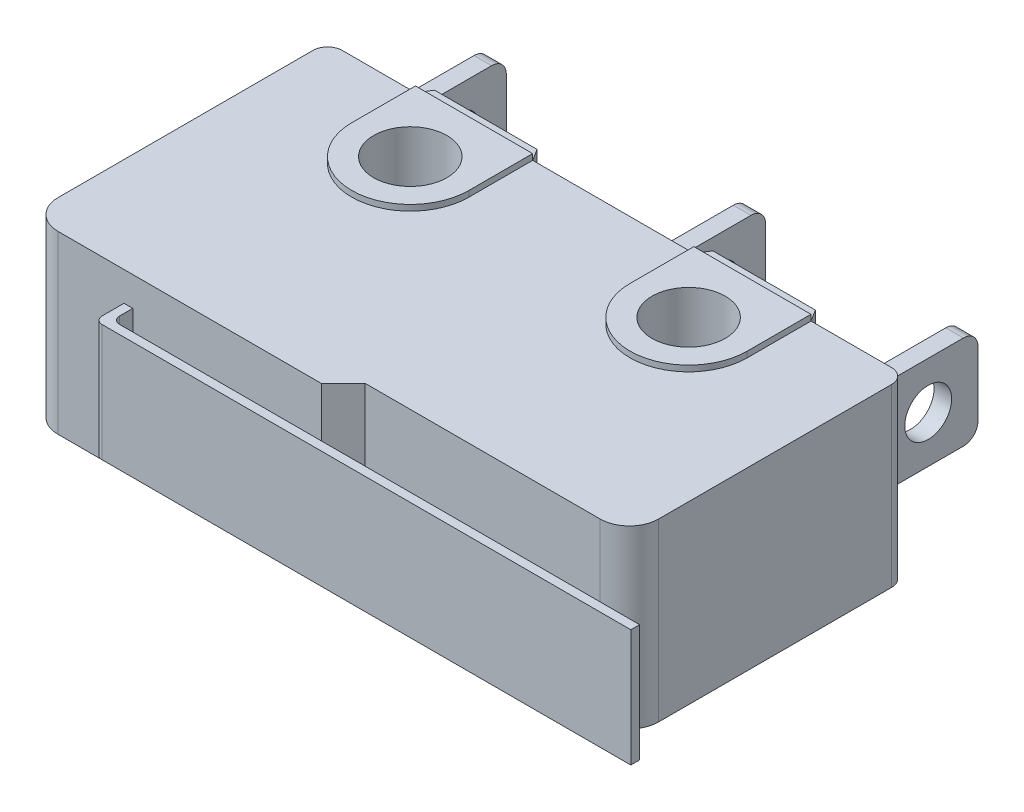
SolidWorks part; units mm, degrees
ref_plane "Front Plane" through (0, 0, 0) normal (0, 0, 1) x (1, 0, 0)
ref_plane "Top Plane" through (0, 0, 0) normal (0, 1, 0) x (1, 0, 0)
ref_plane "Right Plane" through (0, 0, 0) normal (1, 0, 0) x (0, 0, -1)
sketch "Sketch1" plane through (0, 0, 0) normal (0, 1, 0) x (1, 0, 0)
  line L0 (0.1676, 5.122) -> (0.1676, -5.078) construction
  line L1 (-8.8324, -5.078) -> (0.1676, -5.078)
  line L2 (-9.8324, -4.078) -> (-9.8324, 4.622)
  line L3 (-9.3324, 5.122) -> (9.4176, 5.122)
  line L4 (9.9176, -3.328) -> (9.9176, 4.622)
  line L5 (-9.8324, -5.078) -> (9.9176, 5.122) construction
  line L6 (-9.8324, 5.122) -> (9.8569, -5.1347) construction
  line L7 (0.897, -4.328) -> (8.9176, -4.328)
  line L9 (0.1676, -5.078) -> (0.897, -4.328)
  arc A0 (-8.8324, -5.078) -> (-9.8324, -4.078) centre (-8.8324, -4.078) cw
  arc A1 (8.9176, -4.328) -> (9.9176, -3.328) centre (8.9176, -3.328) ccw
  arc A2 (-9.8324, 4.622) -> (-9.3324, 5.122) centre (-9.3324, 4.622) cw
  arc A3 (9.4176, 5.122) -> (9.9176, 4.622) centre (9.4176, 4.622) cw
  point P0 (0, 0)
  dimension "D5" = 1
  dimension "D6" = 0.5
  dimension "D1" = 19.75
  dimension "D2" = 10.2
  dimension "D3" = 10
  dimension "D4" = 9.45
extrude "Boss-Extrude1" add sketch "Sketch1" along normal blind 3 and the other way blind 3
sketch "Sketch2" plane through (0, 0, 0) normal (0, 1, 0) x (1, 0, 0)
  line L0 (-6.5824, 6.1421) -> (-6.5824, -5.078) construction
  line L1 (-9.8324, 4.622) -> (-9.8324, -4.078) construction
  line L2 (-8.8324, -5.078) -> (0.1676, -5.078) construction
  line L4 (-6.5824, -5.078) -> (-6.2824, -5.078)
  line L5 (-6.5824, -5.078) -> (-6.5824, -5.828)
  line L6 (-6.3324, -6.078) -> (-6.2824, -6.078)
  line L7 (-6.2824, -5.078) -> (-6.2824, -5.528)
  line L8 (-6.2824, -6.078) -> (11.7176, -6.078)
  line L10 (-6.0324, -5.778) -> (11.7176, -5.778)
  line L11 (11.7176, -6.078) -> (11.7176, -5.778)
  arc A0 (-6.5824, -5.828) -> (-6.3324, -6.078) centre (-6.3324, -5.828) ccw
  arc A1 (-6.2824, -5.528) -> (-6.0324, -5.778) centre (-6.0324, -5.528) ccw
  dimension "D6" = 0.25
  dimension "D1" = 3.25
  dimension "D2" = 0.3
  dimension "D3" = 1
  dimension "D4" = 0.3
  dimension "D5" = 18
extrude "Boss-Extrude2" add sketch "Sketch2" along normal blind 2 and the other way blind 2
sketch "Sketch3" plane through (0, 3, 0) normal (0, 1, 0) x (1, 0, 0)
  line L0 (9.9176, -3.328) -> (9.9176, 4.622) construction
  circle A0 centre (-4.8324, 2.9447) radius 1.25
  circle A1 centre (4.6676, 2.9447) radius 1.25
  dimension "D1" = 2.5
  dimension "D2" = 9.5
  dimension "D3" = 5.25
sketch "Sketch4" plane through (0, 0, 0) normal (0, 1, 0) x (1, 0, 0)
  line L0 (-6.8324, 2.9447) -> (6.6676, 2.9447) construction
  line L1 (-6.8324, 2.9447) -> (-6.8324, 5.122)
  line L2 (9.4176, 5.122) -> (-9.3324, 5.122) construction
  line L3 (-6.8324, 5.122) -> (-2.8324, 5.122)
  line L4 (6.6676, 5.122) -> (6.6676, 2.9447)
  line L5 (-2.8324, 2.9447) -> (-2.8324, 5.122)
  line L6 (2.6676, 2.9447) -> (2.6676, 5.122)
  line L7 (2.6676, 5.122) -> (6.6676, 5.122)
  line L8 (-0.0824, 5.122) -> (-0.0824, 2.9447) construction
  arc A0 (-6.8324, 2.9447) -> (-2.8324, 2.9447) centre (-4.8324, 2.9447) ccw
  arc A1 (2.6676, 2.9447) -> (6.6676, 2.9447) centre (4.6676, 2.9447) ccw
  dimension "D1" = 4
extrude "Boss-Extrude3" add sketch "Sketch4" along normal blind 3.2 and the other way blind 3.2
extrude "Cut-Extrude1" cut sketch "Sketch3" against normal through all both and the other way through all
sketch "Sketch5" plane through (0, 0, 0) normal (0, 1, 0) x (1, 0, 0)
  line L0 (-6.8324, 5.122) -> (-2.8324, 5.122)
  line L1 (-2.8324, 5.122) -> (-3.0824, 5.522)
  line L2 (-3.0824, 5.522) -> (-6.5824, 5.522)
  line L3 (-6.5824, 5.522) -> (-6.8324, 5.122)
  line L4 (-0.0824, 2.9447) -> (-0.0824, 6.1888) construction
  line L5 (-6.8324, 2.9447) -> (6.6676, 2.9447) construction
  line L6 (6.4176, 5.522) -> (6.6676, 5.122)
  line L7 (2.9176, 5.522) -> (6.4176, 5.522)
  line L8 (2.6676, 5.122) -> (2.9176, 5.522)
  line L9 (6.6676, 5.122) -> (2.6676, 5.122)
  dimension "D1" = 3.5
  dimension "D2" = 0.4
  dimension "D4" = 57.995
extrude "Boss-Extrude4" add sketch "Sketch5" along normal blind 3 and the other way blind 3
sketch "Sketch6" plane through (0, 0, 0) normal (0, 1, 0) x (1, 0, 0)
  line L0 (-6.8324, 5.122) -> (-9.3324, 5.122) construction
  line L1 (-8.3324, 5.122) -> (-7.7324, 5.122)
  line L2 (-8.3324, 5.122) -> (-8.3324, 9.122)
  line L3 (-8.3324, 9.122) -> (-7.7324, 9.122)
  line L4 (-7.7324, 5.122) -> (-7.7324, 9.122)
  line L5 (-9.8324, 4.622) -> (-9.8324, -4.078) construction
  line L6 (9.9176, -3.328) -> (9.9176, 4.622) construction
  line L7 (0.5176, 5.122) -> (1.1176, 5.122)
  line L8 (0.5176, 5.122) -> (0.5176, 9.122)
  line L9 (0.5176, 9.122) -> (1.1176, 9.122)
  line L10 (1.1176, 5.122) -> (1.1176, 9.122)
  line L11 (7.7676, 5.122) -> (8.3676, 5.122)
  line L12 (7.7676, 5.122) -> (7.7676, 9.122)
  line L13 (7.7676, 9.122) -> (8.3676, 9.122)
  line L14 (8.3676, 5.122) -> (8.3676, 9.122)
  dimension "D1" = 0.6
  dimension "D2" = 4
  dimension "D3" = 1.5
  dimension "D4" = 1.55
  dimension "D5" = 8.8
extrude "Boss-Extrude5" add sketch "Sketch6" along normal blind 1.6 and the other way blind 1.6
fillet "Fillet1" radius 0.5 6 edges at (-8.0324, -1.6, -9.122) (0.8176, -1.6, -9.122) (8.0676, -1.6, -9.122) (8.0676, 1.6, -9.122) (0.8176, 1.6, -9.122) (-8.0324, 1.6, -9.122)
sketch "Sketch7" plane through (-8.3324, 0, 0) normal (-1, 0, 0) x (0, 0, 1)
  line L0 (-8.222, -1.6) -> (-8.222, 1.6) construction
  line L1 (-8.622, -1.6) -> (-5.122, -1.6) construction
  line L2 (-8.622, 1.6) -> (-5.122, 1.6) construction
  line L3 (-9.122, 0) -> (-5.122, 0) construction
  line L4 (-9.122, -1.1) -> (-9.122, 1.1) construction
  line L5 (-5.122, -1.6) -> (-5.122, 1.6) construction
  circle A0 centre (-7.422, 0) radius 0.8
  dimension "D2" = 1.6
  dimension "D1" = 0.9
extrude "Cut-Extrude2" cut sketch "Sketch7" against normal through all both and the other way through all
